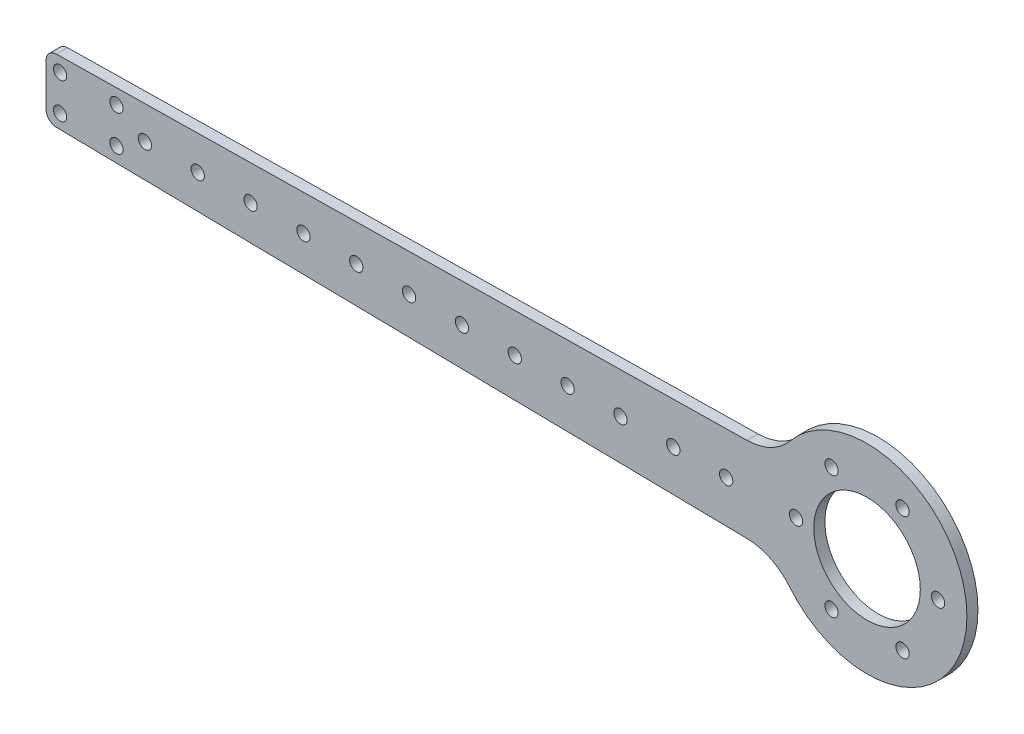
SolidWorks part; units mm, degrees
material "Hexcel AS4C (3000 Filaments)"
ref_plane "Front Plane" through (0, 0, 0) normal (0, 0, 1) x (1, 0, 0)
ref_plane "Top Plane" through (0, 0, 0) normal (0, 1, 0) x (1, 0, 0)
ref_plane "Right Plane" through (0, 0, 0) normal (1, 0, 0) x (0, 0, -1)
sketch "Sketch1" plane through (0, 0, 0) normal (0, 0, 1) x (1, 0, 0)
  line L0 (-100, 0) -> (100, 0) construction
  line L1 (-92.2055, 1.5) -> (77.887, 4.1553)
  line L2 (-96.1462, 6.9392) -> (79.6907, 9.6842)
  line L3 (-92.2055, -1.5) -> (77.887, -4.1553)
  line L4 (-96.1462, -6.9392) -> (79.6907, -9.6842)
  line L5 (-100, 0) -> (-100.1074, -6.8773) construction
  line L6 (-100.1074, -6.8773) -> (-96.1462, -6.9392) construction
  line L7 (-96.1462, 6.9392) -> (-100.1074, 6.8773) construction
  line L8 (-100.1074, 6.8773) -> (-100, 0) construction
  line L9 (-92.2055, 1.5) -> (-92.2055, -1.5)
  circle A0 centre (-100, 0) radius 7.9375 construction
  circle A1 centre (100, 0) radius 22.5 construction
  arc A2 (79.6907, 9.6842) -> (79.6907, -9.6842) centre (100, 0) cw
  arc A3 (77.887, 4.1553) -> (77.887, -4.1553) centre (100, 0) ccw
  arc A4 (-96.1462, 6.9392) -> (-96.1462, -6.9392) centre (-100, 0) ccw
  point P4 (0, 0)
  point P23 (-92.2055, 0)
  dimension "D2" = 15.875
  dimension "D3" = 45
  dimension "D1" = 200
  dimension "D5" = 5.5
  dimension "D6" = 10
  dimension "D7" = 5.5
  dimension "D4" = 10
  dimension "D8" = 3
extrude "Boss-Extrude1" add sketch "Sketch1" along normal mid plane 2.5
fillet "Fillet1" radius 12.7 4 edges at (79.6907, 9.6842, 0) (79.6907, -9.6842, 0) (-96.1462, -6.9392, 0) (-96.1462, 6.9392, 0)
sketch "Sketch2" plane through (0, 0, 0) normal (0, 0, 1) x (1, 0, 0)
  line L8 (-92.2055, 1.5) -> (-92.2055, -1.5) construction
  line L9 (-92.2055, -1.5) -> (77.887, -4.1553) construction
  line L10 (77.887, 4.1553) -> (-92.2055, 1.5) construction
  line L12 (-92.2055, 1.5) -> (-92.2055, -1.5)
  line L13 (-92.2055, -1.5) -> (77.887, -4.1553)
  line L14 (77.887, 4.1553) -> (-92.2055, 1.5)
  arc A6 (77.887, 4.1553) -> (77.887, -4.1553) centre (100, 0) ccw construction
  arc A7 (77.887, 4.1553) -> (77.887, -4.1553) centre (100, 0) ccw
extrude "Boss-Extrude2" add sketch "Sketch2" along normal mid plane 2.5
ref_axis "Axis1" through (100, 0, 1.25) along (0, 0, -1)
ref_axis "Axis2" through (-100, 0, 1.25) along (0, 0, -1)
sketch "Sketch3" plane through (0, 0, 0) normal (0, 0, 1) x (1, 0, 0)
  circle A0 centre (100, 0) radius 12
  dimension "D1" = 24
extrude "Cut-Extrude1" cut sketch "Sketch3" against normal through all both and the other way through all
sketch "Sketch5" plane through (0, 0, 0) normal (0, 0, 1) x (1, 0, 0)
  line L0 (100, 0) -> (116, 0) construction
  circle A0 centre (116, 0) radius 1.5
  dimension "D2" = 3
  dimension "D1" = 16
extrude "Cut-Extrude2" cut sketch "Sketch5" against normal through all both and the other way through all
pattern_circular "CirPattern1" count 6 over 360 about axis through (100, 0, 1.25) along (0, 0, -1) of "Cut-Extrude2"
sketch "Sketch6" plane through (0, 0, 1.25) normal (0, 0, 1) x (1, 0, 0)
  line L0 (100, 0) -> (68.25, 0) construction
  line L1 (-100, 0) -> (-38.9062, 0) construction
  circle A0 centre (68.25, 0) radius 1.5
  circle A1 centre (56.3438, 0) radius 1.5
  circle A2 centre (44.4375, 0) radius 1.5
  circle A3 centre (32.5313, 0) radius 1.5
  circle A4 centre (20.625, 0) radius 1.5
  circle A5 centre (8.7188, 0) radius 1.5
  circle A6 centre (-3.1875, 0) radius 1.5
  circle A7 centre (-15.0937, 0) radius 1.5
  circle A8 centre (-27, 0) radius 1.5
  circle A9 centre (-38.9062, 0) radius 1.5
  circle A10 centre (-50.8125, 0) radius 1.5
  circle A11 centre (-62.7187, 0) radius 1.5
  dimension "D1" = 3
  dimension "D2" = 31.75
  dimension "D4" = 11.9062
  dimension "D3" = 12
extrude "Cut-Extrude3" cut sketch "Sketch6" against normal through all both and the other way through all
sketch "Sketch8" plane through (0, 0, 0) normal (0, 0, 1) x (1, 0, 0)
  line L1 (-115, -25.4) -> (-85, -25.4)
  line L2 (-115, -25.4) -> (-115, 25.4)
  line L3 (-115, 25.4) -> (-85, 25.4)
  line L4 (-85, -25.4) -> (-85, 25.4)
  line L5 (-115, -25.4) -> (-85, 25.4) construction
  line L6 (-115, 25.4) -> (-85, -25.4) construction
  point P0 (-100, 0)
  dimension "D1" = 15
  dimension "D2" = 50.8
extrude "Cut-Extrude4" cut sketch "Sketch8" against normal through all both and the other way through all
fillet "Fillet2" radius 2.3813 2 edges at (-85, -7.1132, 0) (-85, 7.1132, 0)
sketch "Sketch10" plane through (0, 0, 1.25) normal (0, 0, 1) x (1, 0, 0)
  line L0 (-100, 0) -> (-81.825, 0) construction
  line L1 (-85, -4.7688) -> (-85, 4.7688) construction
  line L2 (-81.825, -4) -> (-69.125, -4) construction
  line L3 (-81.825, -4) -> (-81.825, 4) construction
  line L4 (-81.825, 4) -> (-69.125, 4) construction
  line L5 (-69.125, -4) -> (-69.125, 4) construction
  circle A0 centre (-81.825, 4) radius 1.5
  circle A1 centre (-69.125, 4) radius 1.5
  circle A2 centre (-69.125, -4) radius 1.5
  circle A3 centre (-81.825, -4) radius 1.5
  point P8 (-81.825, 0)
  dimension "D4" = 3
  dimension "D1" = 3.175
  dimension "D2" = 12.7
  dimension "D3" = 8
extrude "Cut-Extrude5" cut sketch "Sketch10" against normal through all both and the other way through all
equation "\"length\"= 200mm"
equation "\"D1@Sketch1\"=\"length\""
equation "\"Flange_Pulle\"= 45mm"
equation "\"D3@Sketch1\"=\"Flange_Pulle\""
equation "\"C_Upper\"= 10mm"
equation "\"Upper_Thickness\"= 5.5mm"
equation "\"D5@Sketch1\"=\"Upper_Thickness\""
equation "\"C_Lower\"= 10mm"
equation "\"D6@Sketch1\"=\"C_Lower\""
equation "\"Lower_Thickness\"= 5.5mm"
equation "\"D7@Sketch1\"=\"Lower_Thickness\""
equation "\"Foot_Diameter\"= .625"
equation "\"D2@Sketch1\"=\"Foot_Diameter\""
equation "\"Thicknes\"= 2.5mm"
equation "\"D1@Boss-Extrude1\"=\"Thicknes\""
equation "\"D1@Boss-Extrude2\"=\"Thicknes\""
equation "\"D4@Sketch1\"=\"C_Upper\""
equation "\"m3_clearance\"= 3mm"
equation "\"screw_center_offset\"= 16mm"
equation "\"D2@Sketch5\"=\"m3_clearance\""
equation "\"D1@Sketch5\"=\"screw_center_offset\""
equation "\"D1@Sketch6\"=\"m3_clearance\""
equation "\"I_center_hole_spacing\"=0.46875"
equation "\"D4@Sketch6\"=\"I_center_hole_spacing\""
